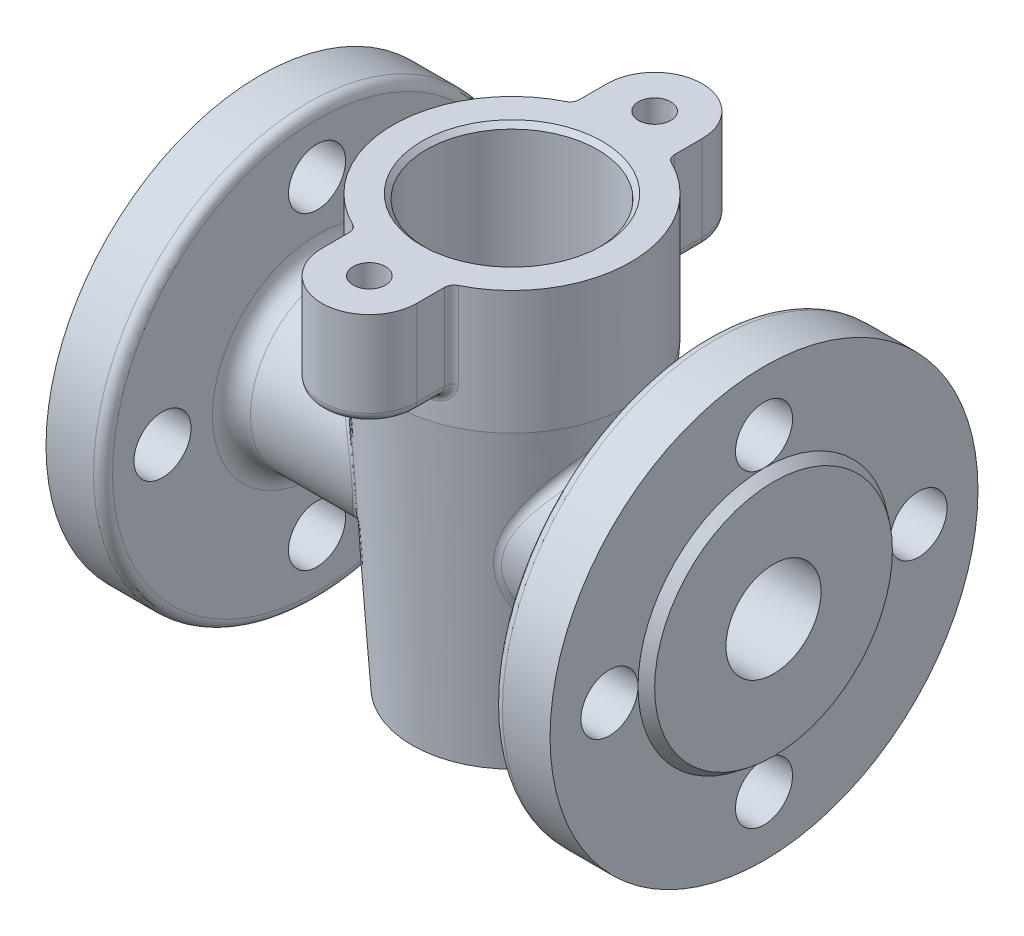
SolidWorks part; units mm, degrees
ref_plane "前视基准面" through (0, 0, 0) normal (0, 0, 1) x (1, 0, 0)
ref_plane "上视基准面" through (0, 0, 0) normal (0, 1, 0) x (1, 0, 0)
ref_plane "右视基准面" through (0, 0, 0) normal (1, 0, 0) x (0, 0, -1)
sketch "草图1" plane through (0, 0, 0) normal (0, 0, 1) x (1, 0, 0)
  line L0 (-70.203, 0) -> (81.9035, 0) construction
  line L1 (0, 77.6671) -> (0, -75.2464) construction
  line L2 (0, 18) -> (41, 18)
  line L3 (41, 18) -> (41, 45)
  line L4 (41, 45) -> (53, 45)
  line L5 (53, 45) -> (53, 26.5)
  line L6 (53, 26.5) -> (55, 25)
  line L7 (55, 25) -> (55, 0)
  line L8 (55, 0) -> (0, 0)
  line L9 (0, 0) -> (0, 18)
  dimension "D1" = 50
  dimension "D2" = 53
  dimension "D3" = 90
  dimension "D4" = 2
  dimension "D5" = 12
  dimension "D6" = 110
  dimension "D7" = 36
revolve "旋转1" add sketch "草图1" angle 360 about L0
hole_wizard "Ø12.0 (12) 直径孔1" positions "草图10" profile "草图9" hole size "Ø12.0" standard "ISO" end condition up to next
sketch "草图10" plane through (53, 0, 0) normal (1, 0, 0) x (0, 0, -1)
  circle A0 centre (0, 0) radius 32.5 construction
  point P0 (0, 32.5)
  dimension "D1" = 65
sketch "草图9" plane through (53, 32.5, 0) normal (0, 1, 0) x (0, 0, -1)
  line L0 (0, 0) -> (0, 12.001)
  line L1 (0, 12.001) -> (6, 12.001)
  line L2 (6, 12.001) -> (6, 0)
  line L5 (6, 0) -> (0, 0)
  line L11 (0, -6.35) -> (0, 107.95) construction
  dimension "通孔孔直径" = 12
  dimension "通孔孔深度" = 12.001
ref_axis "基准轴1" through (53, 0, 0) along (-1, 0, 0)
pattern_circular "阵列(圆周)1" count 4 over 360 about axis through (53, 0, 0) along (-1, 0, 0) of "Ø12.0 (12) 直径孔1"
mirror "镜向1" about plane through (0, 0, 0) normal (1, 0, 0) of "Ø12.0 (12) 直径孔1", "阵列(圆周)1", "旋转1"
sketch "草图2" plane through (0, 0, 0) normal (0, 0, 1) x (1, 0, 0)
  line L0 (0, 61.1937) -> (0, -72.496) construction
  line L1 (0, -40) -> (-21, -40)
  line L2 (-21, -40) -> (-25, 24)
  line L4 (-25, 24) -> (-25, 50)
  line L5 (-25, 50) -> (0, 50)
  line L6 (0, 50) -> (0, -40)
  dimension "D2" = 42
  dimension "D3" = 50
  dimension "D4" = 26
  dimension "D5" = 50
  dimension "D6" = 90
revolve "旋转4" add sketch "草图2" angle 360 about L0
hole_wizard "Ø20.0 (20) 直径孔1" positions "草图4" profile "草图3" hole size "Ø20.0" standard "ISO" end condition through all
sketch "草图4" plane through (55, 0, 0) normal (1, 0, 0) x (0, 0, -1)
  point P0 (0, 0)
sketch "草图3" plane through (55, 0, 0) normal (0, 1, 0) x (0, 0, -1)
  line L0 (0, 0) -> (0, 110)
  line L1 (0, 110) -> (10, 110)
  line L2 (10, 110) -> (10, 0)
  line L5 (10, 0) -> (0, 0)
  line L11 (0, -6.35) -> (0, 107.95) construction
  dimension "通孔孔直径" = 20
  dimension "通孔孔深度" = 110
sketch "草图5" plane through (0, 0, 0) normal (0, 0, 1) x (1, 0, 0)
  line L0 (0, 52.5301) -> (0, -68.2289) construction
  line L1 (18, 50) -> (18, 22)
  line L2 (25, 50) -> (-25, 50) construction
  line L3 (18, 22) -> (14.5, -27)
  line L4 (14.5, -27) -> (16, -27)
  line L5 (16, -27) -> (16, -33)
  line L6 (16, -33) -> (0, -33)
  line L7 (0, -33) -> (0, 50)
  line L8 (0, 50) -> (18, 50)
  line L9 (-21, -40) -> (21, -40) construction
  dimension "D1" = 36
  dimension "D2" = 32
  dimension "D3" = 7
  dimension "D4" = 6
  dimension "D5" = 28
  dimension "D6" = 4.086
revolve "切除-旋转1" cut sketch "草图5" angle 360 about L0
sketch "草图6" plane through (0, 50, 0) normal (0, 1, 0) x (1, 0, 0)
  line L0 (0, 38.5569) -> (0, -64.1323) construction
  line L1 (0, -20.6432) -> (0, -30) construction
  line L2 (10, -22.9129) -> (10, -30)
  line L3 (-10, -22.9129) -> (-10, -30)
  line L4 (-62.9679, 0) -> (65.7588, 0) construction
  arc A1 (-10, -30) -> (10, -30) centre (0, -30) ccw
  circle A2 centre (0, 0) radius 25 construction
  arc A3 (-10, -22.9129) -> (10, -22.9129) centre (0, 0) ccw
  point P5 (0, -31.2517)
  dimension "D2" = 10
  dimension "D1" = 60
extrude "拉伸1" add sketch "草图6" against normal blind 20
hole_wizard "M8 螺纹孔1" positions "草图8" profile "草图7" tap size "M8" standard "ISO" end condition through all
sketch "草图8" plane through (0, 50, 0) normal (0, 1, 0) x (-1, 0, 0)
  point P0 (0, 30)
sketch "草图7" plane through (0, 50, 30) normal (1, 0, 0) x (0, 0, 1)
  line L0 (0, 0) -> (0, 95)
  line L1 (0, 95) -> (3.4, 95)
  line L2 (3.4, 95) -> (3.4, 0)
  line L5 (3.4, 0) -> (0, 0)
  line L11 (0, -6.35) -> (0, 107.95) construction
  dimension "通孔螺纹孔钻头直径" = 6.8
  dimension "通孔螺纹孔钻头深度" = 95
cosmetic thread "孔螺蚊线1" parameters "D2"=8
mirror "镜向2" about plane through (0, 0, 0) normal (0, 0, 1) of "拉伸1", "M8 螺纹孔1"
chamfer "倒角1" distance 1 angle 45 1 edges at (0, 50, 18)
fillet "圆角1" radius 2 12 edges at (-10, 30, -26.4564) (10, 30, -26.4564) (-10, 30, 26.4564) (10, 30, 26.4564) (0, 30, -40) (0, -33, 16) (0, -27, 16) (-41, 0, 45) (41, 0, 45) (21.4409, 13.7915, 11.567) (-21.3365, 13.6451, 11.7393) (0, 30, 40)
fillet "圆角2" radius 2 10 edges at (-10, 41, -22.9129) (-9.6181, 30.8245, -23.0758) (9.3108, 30.4894, -23.2015) (-10, 41, 22.9129) (-9.3108, 30.4894, 23.2015) (9.6181, 30.8245, 23.0758) (10, 41, -22.9129) (10, 41, 22.9129) (0, 30, -25) (0, 30, 25)
fillet "圆角3" radius 4 2 edges at (-41, 0, 18) (41, 0, 18)
equation "\"D6@草图5\" =  atn(   1/14  ) "
